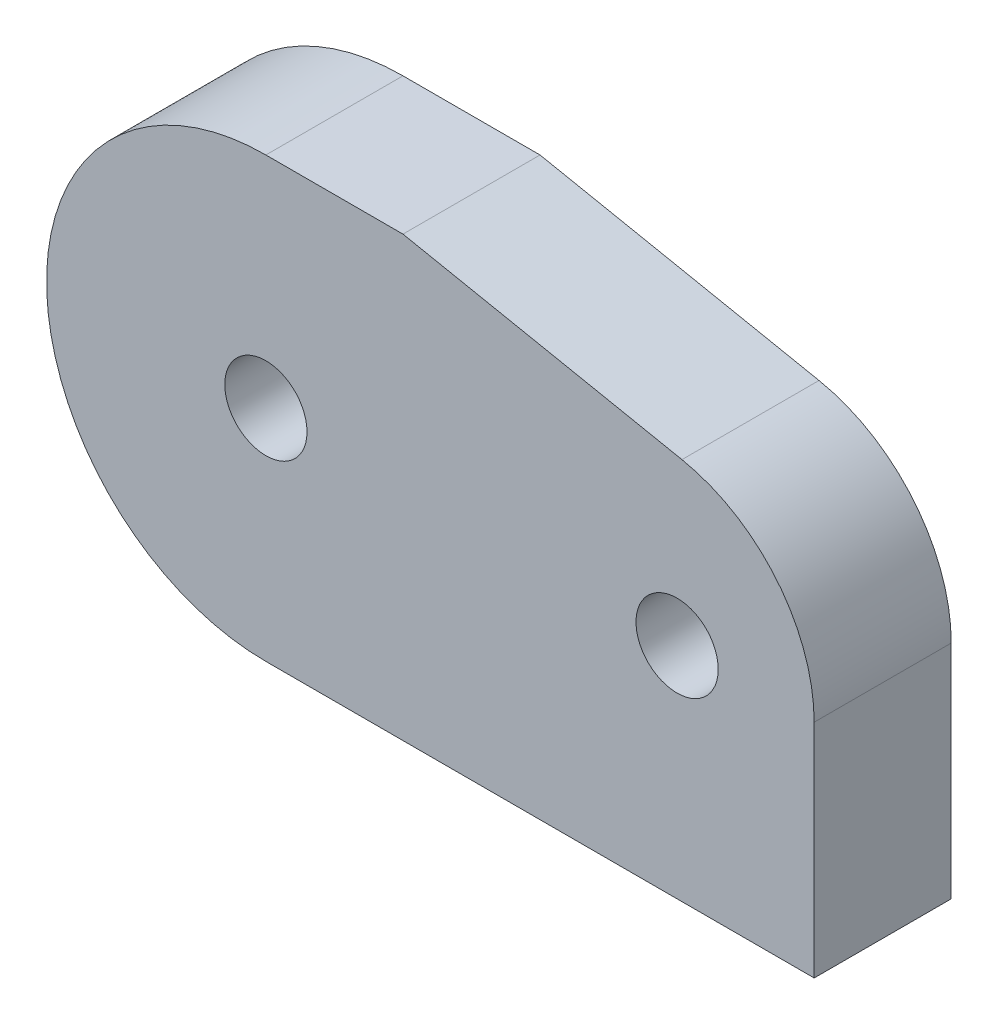
SolidWorks part; units mm, degrees
ref_plane "Plan de face" through (0, 0, 0) normal (0, 0, 1) x (1, 0, 0)
ref_plane "Plan de dessus" through (0, 0, 0) normal (0, 1, 0) x (1, 0, 0)
ref_plane "Plan de droite" through (0, 0, 0) normal (1, 0, 0) x (0, 0, -1)
sketch "Esquisse1" plane through (0, 0, 0) normal (0, 0, 1) x (1, 0, 0)
  line L0 (0, 0) -> (80, 0) construction
  line L1 (20, 0) -> (20, 23.8674) construction
  line L2 (0, 0) -> (0, 35) construction
  line L3 (0, 35) -> (55, 35) construction
  line L4 (0, 8) -> (5, 8)
  line L5 (82.6316, 13.5175) -> (85, 11.6762) construction
  line L6 (20, 8) -> (32.7289, 8) construction
  line L7 (0, -8) -> (55, -8) construction
  line L8 (55, 35) -> (55, -8) construction
  line L9 (0, -8) -> (20, -8)
  line L10 (20, -8) -> (20, 5)
  line L11 (20, 5) -> (5, 8)
  circle A0 centre (0, 0) radius 1.5
  arc A1 (0, 8) -> (0, -8) centre (0, 0) ccw
  circle A2 centre (55, 35) radius 35 construction
  arc A3 (32.7289, 8) -> (82.6316, 13.5175) centre (55, 35) ccw construction
  arc A4 (82.6316, 13.5175) -> (87.5479, 10.0925) centre (85, 11.6762) cw construction
  arc A5 (55, -8) -> (87.5479, 10.0925) centre (55, 30.3227) ccw construction
  circle A6 centre (15, 0) radius 1.5
  dimension "D3" = 3
  dimension "D4" = 35
  dimension "D6" = 70
  dimension "D7" = 3
  dimension "D8" = 8
  dimension "D9" = 30
  dimension "D10" = 15
  dimension "D1" = 20
  dimension "D2" = 80
  dimension "D5" = 55
  dimension "D11" = 13
  dimension "D12" = 15
  dimension "D13" = 20
extrude "Boss.-Extru.1" add sketch "Esquisse1" along normal blind 5
fillet "Congé1" radius 6 1 edges at (20, 5, 2.5)
